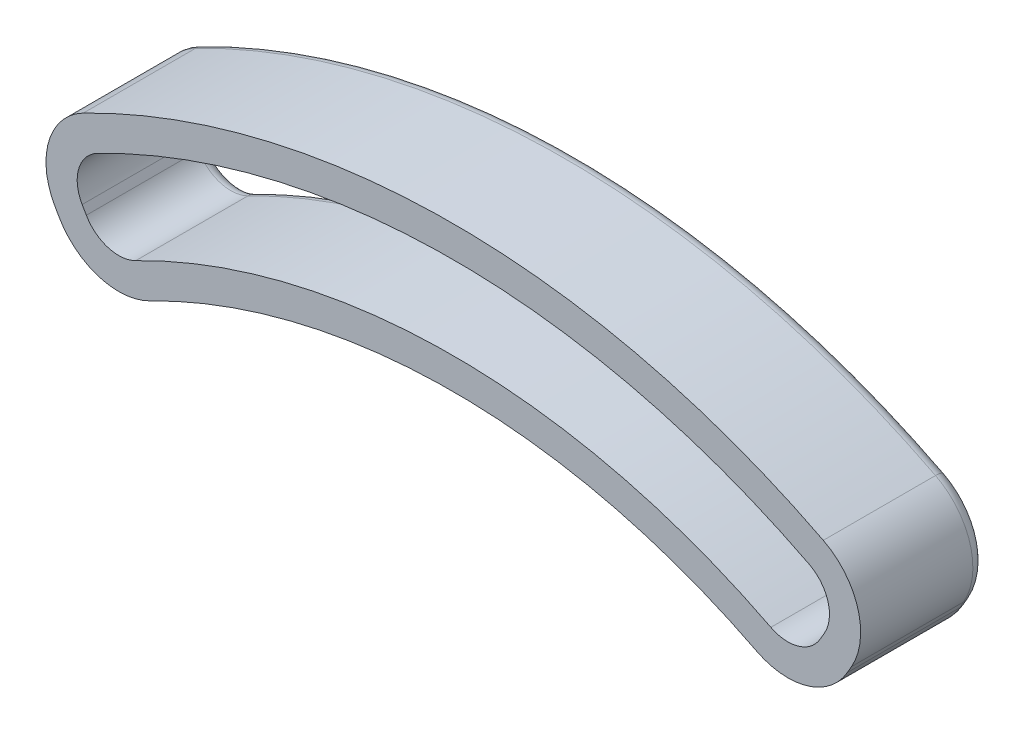
SolidWorks part; units mm, degrees
ref_plane "Front Plane" through (0, 0, 0) normal (0, 0, 1) x (1, 0, 0)
ref_plane "Top Plane" through (0, 0, 0) normal (0, 1, 0) x (1, 0, 0)
ref_plane "Right Plane" through (0, 0, 0) normal (1, 0, 0) x (0, 0, -1)
sketch "Sketch1" plane through (0, 0, 0) normal (0, 0, 1) x (1, 0, 0)
  line L0 (0, 0) -> (0, 42.62) construction
  line L1 (0, 0) -> (-21.31, 36.91) construction
  line L2 (0, 0) -> (21.31, 36.91) construction
  line L3 (-22.4239, 38.8393) -> (-22.6782, 39.2798)
  line L4 (22.4239, 38.8393) -> (22.6782, 39.2798)
  circle A0 centre (0, 0) radius 35 construction
  arc A1 (19.4034, 37.947) -> (-19.4034, 37.947) centre (0, 0) ccw
  arc A2 (21.7404, 42.4576) -> (-21.7404, 42.4576) centre (0, 0) ccw
  arc A3 (-22.4239, 38.8393) -> (-19.4034, 37.947) centre (-20.4442, 39.9823) ccw
  arc A4 (-22.6782, 39.2798) -> (-21.7404, 42.4576) centre (-20.6985, 40.4228) cw
  arc A5 (22.4239, 38.8393) -> (19.4034, 37.947) centre (20.4442, 39.9823) cw
  arc A6 (22.6782, 39.2798) -> (21.7404, 42.4576) centre (20.6985, 40.4228) ccw
  dimension "D1" = 70
  dimension "D2" = 7.62
  dimension "D5" = 5.08
  dimension "D6" = 2.286
  dimension "D3" = 30
  dimension "D4" = 30
extrude "Extrude-Thin2" add sketch "Sketch1" along normal blind 7.62 thin thin type one direction wall 1.905
fillet "Fillet2" radius 0.762 16 edges at (22.891, 41.0699, 0) (22.5511, 39.0596, 0) (21.0918, 37.79, 0) (0, 42.62, 0) (-21.0918, 37.79, 0) (-22.5511, 39.0596, 0) (-22.891, 41.0699, 0) (24.7181, 41.6091, 0) (24.2008, 38.1071, 0) (21.6316, 35.963, 0) (0, 40.715, 0) (-21.6316, 35.963, 0) (-24.2008, 38.1071, 0) (-24.7181, 41.6091, 0) (0, 47.7, 0) (0, 49.605, 0)
